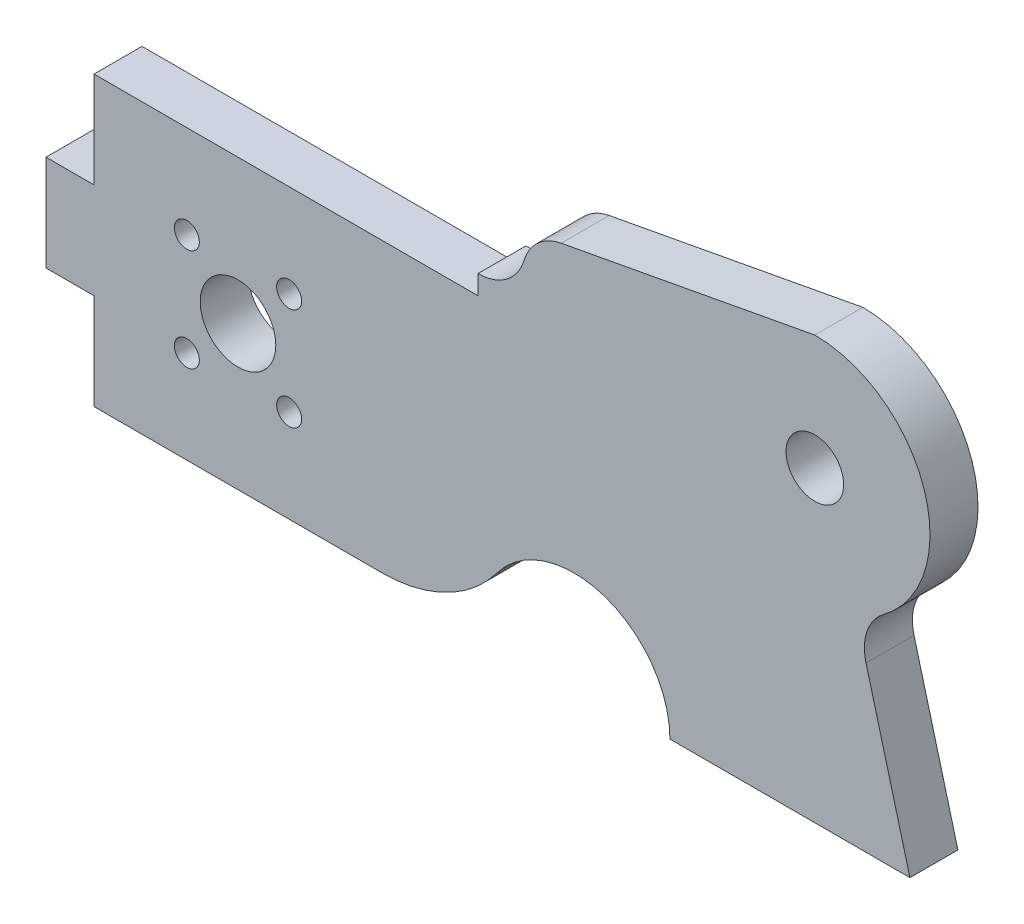
SolidWorks part; units mm, degrees
ref_plane "Front Plane" through (0, 0, 0) normal (0, 0, 1) x (1, 0, 0)
ref_plane "Top Plane" through (0, 0, 0) normal (0, 1, 0) x (1, 0, 0)
ref_plane "Right Plane" through (0, 0, 0) normal (1, 0, 0) x (0, 0, -1)
sketch "Sketch1" plane through (0, 0, 0) normal (0, 0, 1) x (1, 0, 0)
  line L0 (0, 0) -> (107.95, 0)
  line L3 (0, 38.1) -> (0, 25.4)
  line L4 (95.3675, 55.88) -> (0, 38.1)
  line L5 (0, 19.05) -> (100.2273, 19.05) construction
  line L6 (19.05, 19.05) -> (19.05, 28.62) construction
  line L7 (19.05, 19.05) -> (25.817, 25.817) construction
  line L8 (107.95, 0) -> (100.9363, 26.1756)
  line L10 (0, 12.7) -> (0, 0)
  line L11 (0, 25.4) -> (-6.35, 25.4)
  line L13 (0, 12.7) -> (-6.35, 12.7)
  line L14 (-6.35, 25.4) -> (-6.35, 12.7)
  line L15 (100.9363, 26.1756) -> (100.8688, 26.4276)
  arc A0 (100.8688, 26.4276) -> (95.3675, 55.88) centre (95.3675, 40.64) ccw
  circle A1 centre (95.3675, 40.64) radius 3.81
  circle A2 centre (19.05, 19.05) radius 9.57 construction
  circle A3 centre (25.817, 25.817) radius 1.651
  circle A4 centre (25.817, 12.283) radius 1.651
  circle A5 centre (12.283, 12.283) radius 1.651
  circle A6 centre (12.283, 25.817) radius 1.651
  point P26 (19.05, 19.05)
  dimension "D1" = 7.62
  dimension "D5" = 15.24
  dimension "D4" = 19.14
  dimension "D7" = 3.302
  dimension "D11" = 97.0107
  dimension "D2" = 38.1
  dimension "D3" = 40.64
  dimension "D6" = 107.95
  dimension "D8" = 45
  dimension "D9" = 4
  dimension "D10" = 19.05
  dimension "D12" = 75
  dimension "D14" = 12.7
  dimension "D15" = 12.7
  dimension "D16" = 6.35
extrude "Boss-Extrude1" add sketch "Sketch1" along normal blind 6.35
sketch "Sketch2" plane through (0, 0, 6.35) normal (0, 0, 1) x (1, 0, 0)
  circle A0 centre (95.3675, 40.64) radius 38.1 construction
sketch "Sketch3" plane through (0, 0, 0) normal (-1, 0, 0) x (0, 0, 1)
  line L0 (0, 38.1) -> (6.35, 25.4) construction
  line L1 (6.35, 12.7) -> (0, 0) construction
  circle A0 centre (3.175, 31.75) radius 1.5875
  circle A1 centre (3.175, 6.35) radius 1.5875
  dimension "D1" = 3.175
  dimension "D2" = 3.175
extrude "Cut-Extrude1" cut sketch "Sketch3" against normal blind 6.35
sketch "Sketch6" plane through (0, 0, 6.35) normal (0, 0, 1) x (1, 0, 0)
  line L0 (0, 0) -> (107.95, 0) construction
  line L1 (50.8, 0) -> (76.2, 0)
  arc A0 (76.2, 0) -> (50.8, 0) centre (63.5, 0) ccw
  dimension "D1" = 25.4
  dimension "D2" = 31.75
extrude "Cut-Extrude2" cut sketch "Sketch6" against normal blind 6.35
sketch "Sketch7" plane through (0, 0, 6.35) normal (0, 0, 1) x (1, 0, 0)
  line L0 (12.283, 25.817) -> (25.817, 12.283) construction
  line L1 (12.283, 12.283) -> (25.817, 25.817) construction
  circle A0 centre (19.05, 19.05) radius 5
  dimension "D1" = 10
extrude "Cut-Extrude3" cut sketch "Sketch7" against normal through all
fillet "Fillet1" radius 6.35 1 edges at (100.8688, 26.4276, 3.175)
sketch "Sketch8" plane through (0, 0, 6.35) normal (0, 0, 1) x (1, 0, 0)
  line L1 (0, 38.1) -> (50.8, 38.1)
  line L2 (0, 38.1) -> (0, 50.8)
  line L3 (0, 50.8) -> (50.8, 50.8)
  line L4 (50.8, 38.1) -> (50.8, 50.8)
  dimension "D1" = 50.8
  dimension "D2" = 12.7
extrude "Cut-Extrude4" cut sketch "Sketch8" against normal blind 50.8
sketch "Sketch9" plane through (0, 0, 6.35) normal (0, 0, 1) x (1, 0, 0)
  line L3 (50.8, 40.64) -> (57.15, 40.64)
  line L5 (57.15, 40.64) -> (50.8, 40.64)
  line L6 (57.15, 40.64) -> (57.15, 50.8)
  line L7 (57.15, 50.8) -> (50.8, 50.8)
  line L8 (50.8, 40.64) -> (50.8, 50.8)
  line L9 (0, 38.1) -> (50.8, 38.1) construction
  line M8 (50.8, 47.571) -> (50.8, 38.1)
  line M21 (95.3675, 55.88) -> (50.8, 47.571)
  dimension "D1" = 10.16
  dimension "D2" = 2.54
  dimension "D3" = 6.35
extrude "Cut-Extrude5" cut sketch "Sketch9" against normal blind 19.304 contours L3 L6 M21 M8 region at (54.0583, 44.4092, 6.35)
fillet "Fillet6" radius 6.35 1 edges at (57.15, 40.64, 3.175)
fillet "Fillet7" radius 6.35 1 edges at (57.15, 48.7549, 3.175)
fillet "Fillet8" radius 19.05 1 edges at (50.8, 0, 3.175)
sketch "Sketch10" plane through (0, 0, 0) normal (0, -1, 0) x (1, 0, 0)
  line L0 (107.95, 6.35) -> (107.95, 0) construction
  line L1 (76.2, 6.35) -> (107.95, 6.35) construction
  line L2 (0, 6.35) -> (38.1, 6.35) construction
  line L3 (38.1, 0) -> (38.1, 6.35) construction
  circle A0 centre (92.075, 3.175) radius 1.5875
  circle A1 centre (19.05, 3.175) radius 1.5875
  point P5 (107.95, 3.175)
  point P8 (92.075, 6.35)
  point P12 (19.05, 6.35)
  point P13 (0, 0)
  point P16 (38.1, 3.175)
  dimension "D1" = 3.175
